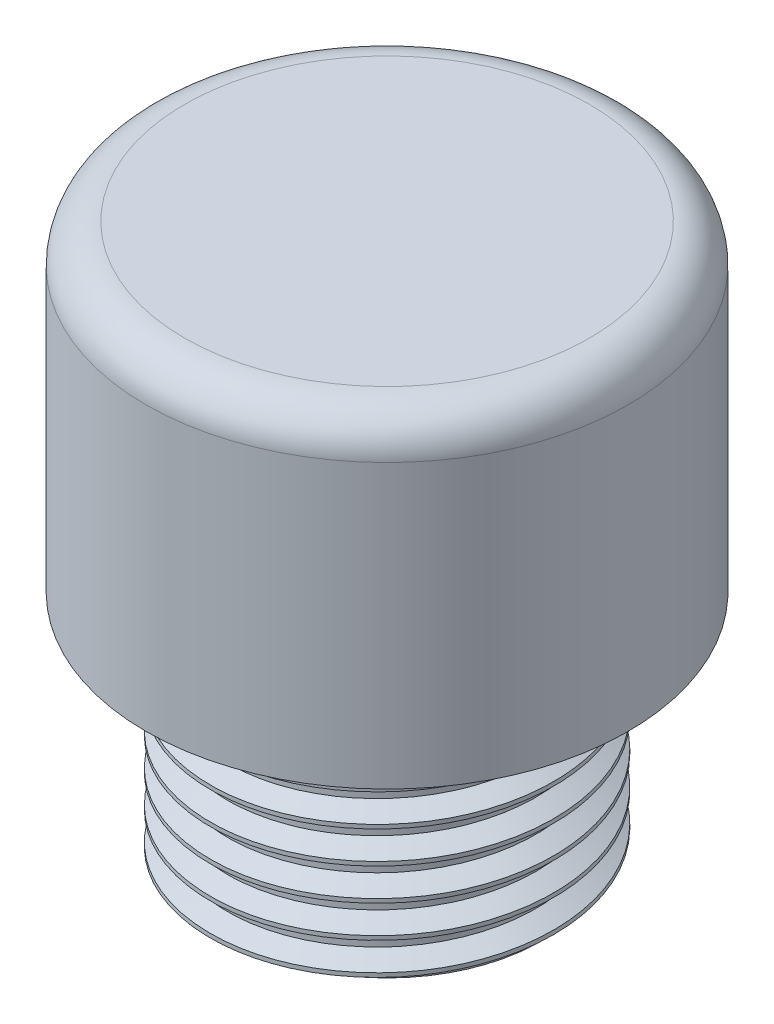
SolidWorks part; units mm, degrees
note: The reader was unsure of these and kept them because the rebuilt part matched: shared geometry of "Sketch1<3>", "Sketch1<5>".
ref_plane "Front Plane" through (0, 0, 0) normal (0, 0, 1) x (1, 0, 0)
ref_plane "Top Plane" through (0, 0, 0) normal (0, 1, 0) x (1, 0, 0)
ref_plane "Right Plane" through (0, 0, 0) normal (1, 0, 0) x (0, 0, -1)
sketch "Sketch1" plane through (0, 0, 0) normal (0, 1, 0) x (1, 0, 0)
  line L1 (-3.3655, -3.3655) -> (3.3655, -3.3655)
  line L2 (-3.3655, -3.3655) -> (-3.3655, 3.3655)
  line L3 (-3.3655, 3.3655) -> (3.3655, 3.3655)
  line L4 (3.3655, -3.3655) -> (3.3655, 3.3655)
  line L5 (-3.3655, -3.3655) -> (3.3655, 3.3655) construction
  line L6 (-3.3655, 3.3655) -> (3.3655, -3.3655) construction
  circle A0 centre (0, 0) radius 9.525
  circle A1 centre (0, 0) radius 6.096
  circle A2 centre (0, 0) radius 2.5 construction
  dimension "D1" = 5
  dimension "D2" = 19.05
  dimension "D3" = 12.192
  dimension "D4" = 6.731
  dimension "D5" = 6.731
extrude "Boss-Extrude1" add sketch "Sketch1" along normal blind 12.7 contours A0 A1 | A1 L4 L1 L2 L3 | L1 L4 L3 L2
extrude "Boss-Extrude2" add sketch "Sketch1<3>" against normal blind 8.89 contours A1 L4 L1 L2 L3 | L1 L4 L3 L2
sketch "Sketch1<3>" plane through (0, 0, 0) normal (0, 1, 0) x (1, 0, 0) same geometry as "Sketch1"
extrude "Cut-Extrude1" cut sketch "Sketch1<5>" against normal blind 6.731 from offset 12.192 contours L1 L4 L3 L2
sketch "Sketch1<5>" plane through (0, 0, 0) normal (0, 1, 0) x (1, 0, 0) same geometry as "Sketch1"
thread "Thread1" pitch 1.27 start angle 0, offset 6.08, length 0, pitch 1.27, diameter 12.192
ref_plane "Plane2" through (6.096, -14.97, 0) normal (0, 0, 1) x (1, 0, 0)
sketch "Thread Profile2" plane through (6.096, -14.97, 0) normal (0, 0, 1) x (1, 0, 0)
  line L0 (0, 0) -> (0, 1.27) construction
  line L1 (0, 0) -> (0.6874, 0.3969)
  line L2 (0.6874, 0.3969) -> (0.6874, 0.5556)
  line L3 (0.6874, 0.5556) -> (0, 0.9525)
  line L4 (0.6874, 0.4762) -> (0, 0.4762) construction
  line L11 (0, 0) -> (0, 0.9525)
  point P2 (0, 0)
  dimension "Pitch" = 1.27
  dimension "Profile_Angle" = 60
  dimension "Profile_Land" = 0.1588
  dimension "Profile_Height" = 0.6874
fillet "Fillet1" radius 1.524 1 edges at (0, 12.7, 9.525)
sketch "Sketch2" plane through (0, 0, 0) normal (0, -1, 0) x (1, 0, 0)
  circle A0 centre (0, 0) radius 3.81
  dimension "D1" = 7.62
extrude "Cut-Extrude2" cut sketch "Sketch2" along normal up to surface (8.89 mm away) up to face at (-1.3843, -8.89, 0.0542)
chamfer "Chamfer1" distance 2.54 distance2 3.048 1 edges at (0, 0, -3.81)
equation "\"CIRC.MAGNET.DIA\"=0.19685"
equation "\"D1@Sketch1\"=\"CIRC.MAGNET.DIA\""
equation "\"SQR.MAGNET.L\"=0.265"
equation "\"D4@Sketch1\"=\"SQR.MAGNET.L\""
equation "\"D1@Cut-Extrude1\"=\"SQR.MAGNET.L\""
